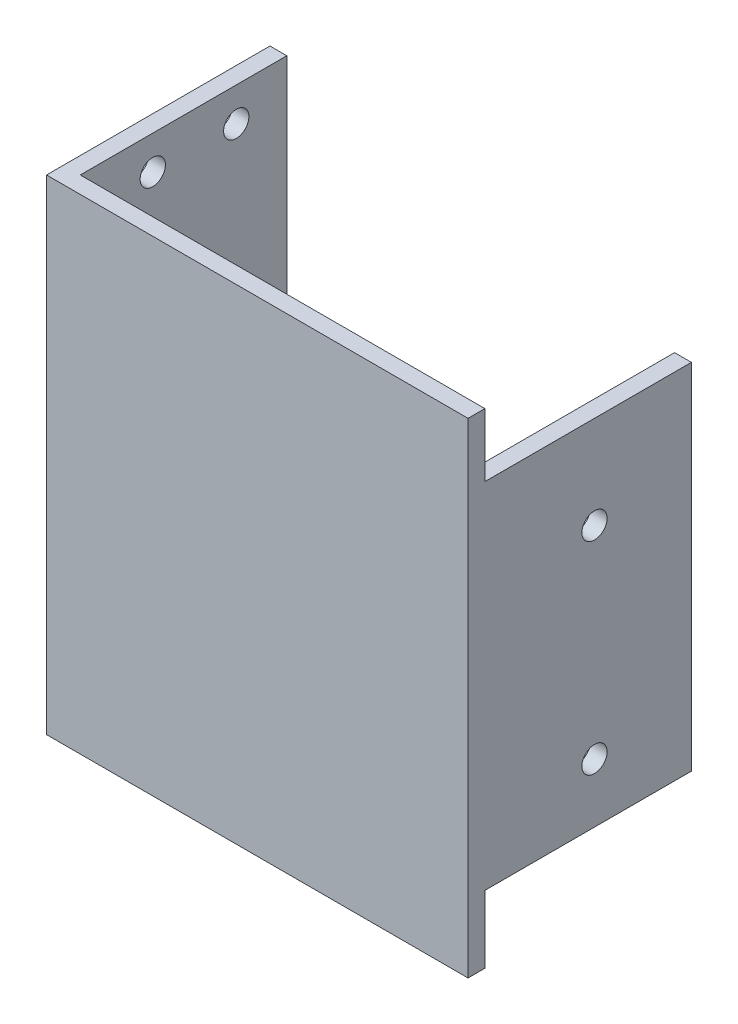
SolidWorks part; units mm, degrees
ref_plane "前视基准面" through (0, 0, 0) normal (0, 0, 1) x (1, 0, 0)
ref_plane "上视基准面" through (0, 0, 0) normal (0, 1, 0) x (1, 0, 0)
ref_plane "右视基准面" through (0, 0, 0) normal (1, 0, 0) x (0, 0, -1)
other "Configuration Table"
sketch "草图1" plane through (0, 0, 0) normal (0, 0, 1) x (1, 0, 0)
  line L1 (-20, 37.5) -> (20, 37.5)
  line L2 (-20, 37.5) -> (-20, -37.5)
  line L3 (-20, -37.5) -> (20, -37.5)
  line L4 (20, 37.5) -> (20, -37.5)
  dimension "D1" = 75
  dimension "D2" = 40
  dimension "D3" = 20
  dimension "D4" = 37.5
extrude "凸台-拉伸1" add sketch "草图1" along normal blind 21
fillet "圆角1" radius 20 2 edges at (-20, 37.5, 10.5) (20, 37.5, 10.5)
chamfer "倒角1" distance 10 angle 45 2 edges at (-20, -37.5, 10.5) (20, -37.5, 10.5)
sketch "草图2" plane through (0, 0, 0) normal (0, 0, -1) x (-1, 0, 0)
  line L0 (10, -37.5) -> (-10, -37.5) construction
  line L1 (-10, -37.5) -> (10, -37.5)
  line L2 (10, -37.5) -> (14.4499, -21.5251)
  line L3 (-10, -37.5) -> (-14.4499, -21.5251)
  arc A0 (14.4499, -21.5251) -> (-14.4499, -21.5251) centre (0, -17.5) ccw
  circle A1 centre (0, -17.5) radius 20 construction
  dimension "D1" = 30
  dimension "D2" = 40
extrude "凸台-拉伸2" add sketch "草图2" along normal blind 700
sketch "草图3" plane through (0, 0, 0) normal (0, 0, -1) x (-1, 0, 0)
  circle A0 centre (0, 17.5) radius 19
  arc A1 (20, 17.5) -> (0, 37.5) centre (0, 17.5) ccw construction
  dimension "D1" = 38
extrude "凸台-拉伸4" add sketch "草图3" along normal blind 74
sketch "草图4" plane through (0, 0, 21) normal (0, 0, 1) x (1, 0, 0)
  line L0 (-10, -37.5) -> (10, -37.5) construction
  line L1 (-8.5, -8) -> (8.5, -8)
  line L2 (-8.5, -8) -> (-8.5, -25)
  line L3 (-8.5, -25) -> (8.5, -25)
  line L4 (8.5, -8) -> (8.5, -25)
  dimension "D1" = 17
  dimension "D2" = 8.5
  dimension "D3" = 12.5
extrude "凸台-拉伸5" add sketch "草图4" along normal blind 19
sketch "草图5" plane through (-8.5, 0, 0) normal (-1, 0, 0) x (0, 0, 1)
  line L0 (40, -8) -> (40, -25) construction
  line L1 (40, -8) -> (21, -8) construction
  circle A0 centre (31.5, -16.5) radius 3
  dimension "D1" = 8.5
  dimension "D2" = 6
  dimension "D3" = 8.5
extrude "切除-拉伸1" cut sketch "草图5" against normal blind 19
sketch "草图6" plane through (0, 0, -700) normal (0, 0, -1) x (-1, 0, 0)
  circle A0 centre (0, -17.5) radius 10
  dimension "D1" = 20
extrude "凸台-拉伸6" add sketch "草图6" along normal blind 16.5
sketch "草图7" plane through (0, 0, -716.5) normal (0, 0, -1) x (-1, 0, 0)
  circle A0 centre (0, -17.5) radius 20
  dimension "D1" = 40
extrude "凸台-拉伸7" add sketch "草图7" along normal blind 20
sketch "草图8" plane through (0, 0, -736.5) normal (0, 0, -1) x (-1, 0, 0)
  line L1 (-25, 11.25) -> (25, 11.25)
  line L2 (-25, 11.25) -> (-25, -46.25)
  line L3 (-25, -46.25) -> (25, -46.25)
  line L4 (25, 11.25) -> (25, -46.25)
  circle A0 centre (0, -17.5) radius 20 construction
  dimension "D4" = 28.75
  dimension "D1" = 57.5
  dimension "D2" = 50
  dimension "D3" = 25
extrude "凸台-拉伸8" add sketch "草图8" along normal blind 2
sketch "草图9" plane through (0, 0, -738.5) normal (0, 0, -1) x (-1, 0, 0)
  line L0 (-25, -46.25) -> (25, -46.25) construction
  line L1 (25, 11.25) -> (23, 11.25)
  line L2 (25, 11.25) -> (25, -46.25)
  line L3 (25, -46.25) -> (23, -46.25)
  line L4 (23, 11.25) -> (23, -46.25)
  dimension "D1" = 2
extrude "凸台-拉伸9" add sketch "草图9" along normal blind 24.5
sketch "草图10" plane through (0, 0, -738.5) normal (0, 0, -1) x (-1, 0, 0)
  line L0 (-25, 11.25) -> (-25, -46.25) construction
  line L1 (-25, 3.75) -> (-23, 3.75)
  line L2 (-25, 3.75) -> (-25, -38.25)
  line L3 (-25, -38.25) -> (-23, -38.25)
  line L4 (-23, 3.75) -> (-23, -38.25)
  line L5 (23, 11.25) -> (-25, 11.25) construction
  dimension "D1" = 42
  dimension "D2" = 7.5
  dimension "D3" = 2
extrude "凸台-拉伸10" add sketch "草图10" along normal blind 24.5
sketch "草图11" plane through (-25, 0, 0) normal (-1, 0, 0) x (0, 0, 1)
  line L0 (-763, -46.25) -> (-763, 11.25) construction
  line L1 (-757, 7.25) -> (-747.1, 7.25) construction
  line L2 (-757, 7.25) -> (-757, -41.75) construction
  line L3 (-757, -41.75) -> (-747.1, -41.75) construction
  line L4 (-747.1, 7.25) -> (-747.1, -41.75) construction
  line L5 (-763, 11.25) -> (-736.5, 11.25) construction
  circle A0 centre (-757, 7.25) radius 1.5
  circle A1 centre (-747.1, 7.25) radius 1.5
  circle A2 centre (-747.1, -41.75) radius 1.5
  circle A3 centre (-757, -41.75) radius 1.5
  dimension "D5" = 3
  dimension "D1" = 9.9
  dimension "D2" = 49
  dimension "D3" = 6
  dimension "D4" = 4
extrude "切除-拉伸2" cut sketch "草图11" against normal blind 10
sketch "草图12" plane through (-25, 0, 0) normal (-1, 0, 0) x (0, 0, 1)
  circle A1 centre (-752.05, -31.25) radius 1.5
  circle A2 centre (-747.1, -41.75) radius 1.5 construction
  circle A3 centre (-757, -41.75) radius 1.5 construction
  dimension "D1" = 10.5
  dimension "D2" = 4.95
  dimension "D3" = 3
extrude "切除-拉伸3" cut sketch "草图12" against normal blind 10
sketch "草图13" plane through (25, 0, 0) normal (1, 0, 0) x (0, 0, -1)
  line L0 (763, 3.75) -> (738.5, 3.75) construction
  line L2 (763, 3.75) -> (763, -38.25) construction
  circle A0 centre (751.5, -7.25) radius 1.5
  circle A1 centre (751.5, -31.25) radius 1.5
  dimension "D1" = 24
  dimension "D4" = 3
  dimension "D5" = 3
  dimension "D2" = 11
  dimension "D3" = 11.5
extrude "切除-拉伸4" cut sketch "草图13" against normal blind 10
sketch "草图14" plane through (-25, 0, 0) normal (-1, 0, 0) x (0, 0, 1)
  line L1 (-736.5, 105.5485) -> (74.8099, 105.5485)
  line L2 (-736.5, 105.5485) -> (-736.5, -178.1721)
  line L3 (-736.5, -178.1721) -> (74.8099, -178.1721)
  line L4 (74.8099, 105.5485) -> (74.8099, -178.1721)
extrude "切除-拉伸5" cut sketch "草图14" against normal through all both and the other way through all
